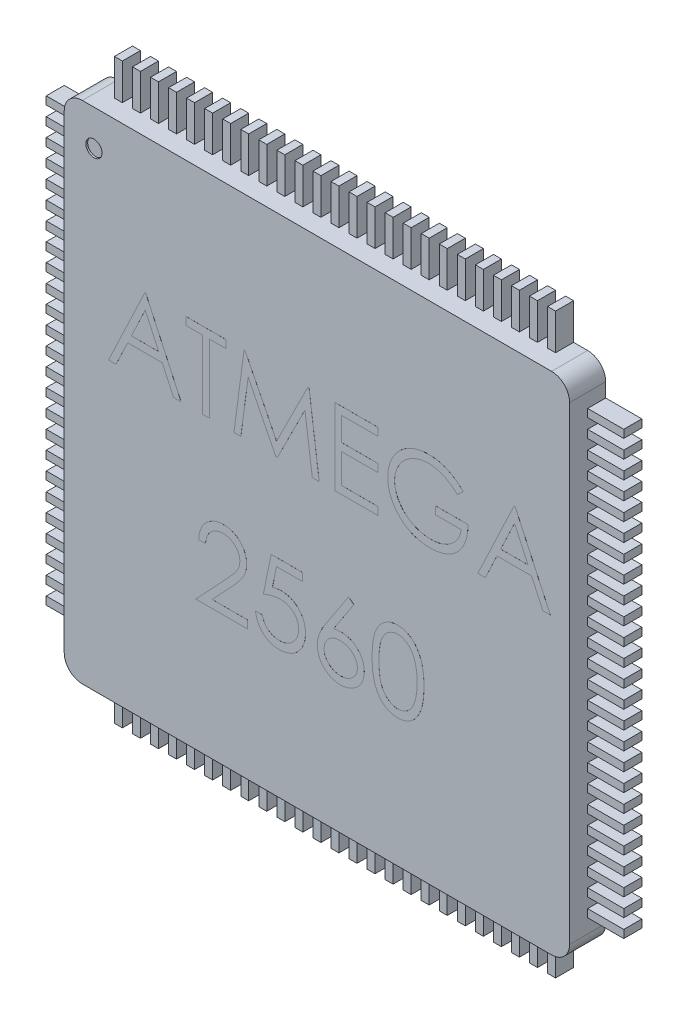
SolidWorks part; units mm, degrees
ref_plane "Plan de face" through (0, 0, 0) normal (0, 0, 1) x (1, 0, 0)
ref_plane "Plan de dessus" through (0, 0, 0) normal (0, 1, 0) x (1, 0, 0)
ref_plane "Plan de droite" through (0, 0, 0) normal (1, 0, 0) x (0, 0, -1)
sketch "Sketch1" plane through (0, 0, 0) normal (0, 0, 1) x (1, 0, 0)
  line L1 (6.5, 7) -> (-6.5, 7)
  line L2 (7, 6.5) -> (7, -6.5)
  line L3 (6.5, -7) -> (-6.5, -7)
  line L4 (-7, 6.5) -> (-7, -6.5)
  line L5 (7, 7) -> (-7, -7) construction
  line L6 (7, -7) -> (-7, 7) construction
  line L7 (-8, 8) -> (8, 8) construction
  line L8 (-8, 8) -> (-8, -8) construction
  line L9 (-8, -8) -> (8, -8) construction
  line L10 (8, 8) -> (8, -8) construction
  line L11 (-8, 8) -> (8, -8) construction
  line L12 (-8, -8) -> (8, 8) construction
  arc A0 (-6.5, -7) -> (-7, -6.5) centre (-6.5, -6.5) cw
  arc A1 (7, -6.5) -> (6.5, -7) centre (6.5, -6.5) cw
  arc A2 (6.5, 7) -> (7, 6.5) centre (6.5, 6.5) cw
  arc A3 (-6.5, 7) -> (-7, 6.5) centre (-6.5, 6.5) ccw
  point P0 (0, 0)
  point P6 (0, 0)
  dimension "D5" = 0.5
  dimension "D1" = 14
  dimension "D2" = 14
  dimension "D3" = 16
  dimension "D4" = 16
extrude "Boss-Extrude1" add sketch "Sketch1" along normal blind 1
sketch "Sketch3" plane through (0, 0, 0) normal (0, 0, 1) x (1, 0, 0)
  line L0 (7, 0) -> (-7, 0) construction
  line L1 (7, -6.5) -> (7, 6.5) construction
  line L2 (-7, 6.5) -> (-7, -6.5) construction
  line L3 (0, 7) -> (0, -7) construction
  line L6 (7, -0.11) -> (8, -0.11)
  line L7 (8, -0.11) -> (8, 0.11)
  line L8 (8, 0.11) -> (7, 0.11)
  line L9 (7, 0.11) -> (7, -0.11)
  line L10 (7, 0.39) -> (8, 0.39)
  line L11 (8, 0.39) -> (8, 0.61)
  line L12 (8, 0.61) -> (7, 0.61)
  line L13 (7, 0.61) -> (7, 0.39)
  line L14 (7, 0.89) -> (8, 0.89)
  line L15 (8, 0.89) -> (8, 1.11)
  line L16 (8, 1.11) -> (7, 1.11)
  line L17 (7, 1.11) -> (7, 0.89)
  line L18 (7, 1.39) -> (8, 1.39)
  line L19 (8, 1.39) -> (8, 1.61)
  line L20 (8, 1.61) -> (7, 1.61)
  line L21 (7, 1.61) -> (7, 1.39)
  line L22 (7, 1.89) -> (8, 1.89)
  line L23 (8, 1.89) -> (8, 2.11)
  line L24 (8, 2.11) -> (7, 2.11)
  line L25 (7, 2.11) -> (7, 1.89)
  line L26 (7, 2.39) -> (8, 2.39)
  line L27 (8, 2.39) -> (8, 2.61)
  line L28 (8, 2.61) -> (7, 2.61)
  line L29 (7, 2.61) -> (7, 2.39)
  line L30 (7, 2.89) -> (8, 2.89)
  line L31 (8, 2.89) -> (8, 3.11)
  line L32 (8, 3.11) -> (7, 3.11)
  line L33 (7, 3.11) -> (7, 2.89)
  line L34 (7, 3.39) -> (8, 3.39)
  line L35 (8, 3.39) -> (8, 3.61)
  line L36 (8, 3.61) -> (7, 3.61)
  line L37 (7, 3.61) -> (7, 3.39)
  line L38 (7, 3.89) -> (8, 3.89)
  line L39 (8, 3.89) -> (8, 4.11)
  line L40 (8, 4.11) -> (7, 4.11)
  line L41 (7, 4.11) -> (7, 3.89)
  line L42 (7, 4.39) -> (8, 4.39)
  line L43 (8, 4.39) -> (8, 4.61)
  line L44 (8, 4.61) -> (7, 4.61)
  line L45 (7, 4.61) -> (7, 4.39)
  line L46 (7, 4.89) -> (8, 4.89)
  line L47 (8, 4.89) -> (8, 5.11)
  line L48 (8, 5.11) -> (7, 5.11)
  line L49 (7, 5.11) -> (7, 4.89)
  line L50 (7, 5.39) -> (8, 5.39)
  line L51 (8, 5.39) -> (8, 5.61)
  line L52 (8, 5.61) -> (7, 5.61)
  line L53 (7, 5.61) -> (7, 5.39)
  line L54 (7, 5.89) -> (8, 5.89)
  line L55 (8, 5.89) -> (8, 6.11)
  line L56 (8, 6.11) -> (7, 6.11)
  line L57 (7, 6.11) -> (7, 5.89)
  line L58 (7, -6.11) -> (7, -5.89)
  line L59 (8, -6.11) -> (7, -6.11)
  line L60 (8, -5.89) -> (8, -6.11)
  line L61 (7, -5.89) -> (8, -5.89)
  line L62 (7, -5.61) -> (7, -5.39)
  line L63 (8, -5.61) -> (7, -5.61)
  line L64 (8, -5.39) -> (8, -5.61)
  line L65 (7, -5.39) -> (8, -5.39)
  line L66 (7, -5.11) -> (7, -4.89)
  line L67 (8, -5.11) -> (7, -5.11)
  line L68 (8, -4.89) -> (8, -5.11)
  line L69 (7, -4.89) -> (8, -4.89)
  line L70 (7, -4.61) -> (7, -4.39)
  line L71 (8, -4.61) -> (7, -4.61)
  line L72 (8, -4.39) -> (8, -4.61)
  line L73 (7, -4.39) -> (8, -4.39)
  line L74 (7, -4.11) -> (7, -3.89)
  line L75 (8, -4.11) -> (7, -4.11)
  line L76 (8, -3.89) -> (8, -4.11)
  line L77 (7, -3.89) -> (8, -3.89)
  line L78 (7, -3.61) -> (7, -3.39)
  line L79 (8, -3.61) -> (7, -3.61)
  line L80 (8, -3.39) -> (8, -3.61)
  line L81 (7, -3.39) -> (8, -3.39)
  line L82 (7, -3.11) -> (7, -2.89)
  line L83 (8, -3.11) -> (7, -3.11)
  line L84 (8, -2.89) -> (8, -3.11)
  line L85 (7, -2.89) -> (8, -2.89)
  line L86 (7, -2.61) -> (7, -2.39)
  line L87 (8, -2.61) -> (7, -2.61)
  line L88 (8, -2.39) -> (8, -2.61)
  line L89 (7, -2.39) -> (8, -2.39)
  line L90 (7, -2.11) -> (7, -1.89)
  line L91 (8, -2.11) -> (7, -2.11)
  line L92 (8, -1.89) -> (8, -2.11)
  line L93 (7, -1.89) -> (8, -1.89)
  line L94 (7, -1.61) -> (7, -1.39)
  line L95 (8, -1.61) -> (7, -1.61)
  line L96 (8, -1.39) -> (8, -1.61)
  line L97 (7, -1.39) -> (8, -1.39)
  line L98 (7, -1.11) -> (7, -0.89)
  line L99 (8, -1.11) -> (7, -1.11)
  line L100 (8, -0.89) -> (8, -1.11)
  line L101 (7, -0.89) -> (8, -0.89)
  line L102 (7, -0.61) -> (7, -0.39)
  line L103 (8, -0.61) -> (7, -0.61)
  line L104 (8, -0.39) -> (8, -0.61)
  line L105 (7, -0.39) -> (8, -0.39)
  line L106 (-7, -0.39) -> (-8, -0.39)
  line L107 (-8, -0.39) -> (-8, -0.61)
  line L108 (-8, -0.61) -> (-7, -0.61)
  line L109 (-7, -0.61) -> (-7, -0.39)
  line L110 (-7, -0.89) -> (-8, -0.89)
  line L111 (-8, -0.89) -> (-8, -1.11)
  line L112 (-8, -1.11) -> (-7, -1.11)
  line L113 (-7, -1.11) -> (-7, -0.89)
  line L114 (-7, -1.39) -> (-8, -1.39)
  line L115 (-8, -1.39) -> (-8, -1.61)
  line L116 (-8, -1.61) -> (-7, -1.61)
  line L117 (-7, -1.61) -> (-7, -1.39)
  line L118 (-7, -1.89) -> (-8, -1.89)
  line L119 (-8, -1.89) -> (-8, -2.11)
  line L120 (-8, -2.11) -> (-7, -2.11)
  line L121 (-7, -2.11) -> (-7, -1.89)
  line L122 (-7, -2.39) -> (-8, -2.39)
  line L123 (-8, -2.39) -> (-8, -2.61)
  line L124 (-8, -2.61) -> (-7, -2.61)
  line L125 (-7, -2.61) -> (-7, -2.39)
  line L126 (-7, -2.89) -> (-8, -2.89)
  line L127 (-8, -2.89) -> (-8, -3.11)
  line L128 (-8, -3.11) -> (-7, -3.11)
  line L129 (-7, -3.11) -> (-7, -2.89)
  line L130 (-7, -3.39) -> (-8, -3.39)
  line L131 (-8, -3.39) -> (-8, -3.61)
  line L132 (-8, -3.61) -> (-7, -3.61)
  line L133 (-7, -3.61) -> (-7, -3.39)
  line L134 (-7, -3.89) -> (-8, -3.89)
  line L135 (-8, -3.89) -> (-8, -4.11)
  line L136 (-8, -4.11) -> (-7, -4.11)
  line L137 (-7, -4.11) -> (-7, -3.89)
  line L138 (-7, -4.39) -> (-8, -4.39)
  line L139 (-8, -4.39) -> (-8, -4.61)
  line L140 (-8, -4.61) -> (-7, -4.61)
  line L141 (-7, -4.61) -> (-7, -4.39)
  line L142 (-7, -4.89) -> (-8, -4.89)
  line L143 (-8, -4.89) -> (-8, -5.11)
  line L144 (-8, -5.11) -> (-7, -5.11)
  line L145 (-7, -5.11) -> (-7, -4.89)
  line L146 (-7, -5.39) -> (-8, -5.39)
  line L147 (-8, -5.39) -> (-8, -5.61)
  line L148 (-8, -5.61) -> (-7, -5.61)
  line L149 (-7, -5.61) -> (-7, -5.39)
  line L150 (-7, -5.89) -> (-8, -5.89)
  line L151 (-8, -5.89) -> (-8, -6.11)
  line L152 (-8, -6.11) -> (-7, -6.11)
  line L153 (-7, -6.11) -> (-7, -5.89)
  line L154 (-7, 6.11) -> (-7, 5.89)
  line L155 (-8, 6.11) -> (-7, 6.11)
  line L156 (-8, 5.89) -> (-8, 6.11)
  line L157 (-7, 5.89) -> (-8, 5.89)
  line L158 (-7, 5.61) -> (-7, 5.39)
  line L159 (-8, 5.61) -> (-7, 5.61)
  line L160 (-8, 5.39) -> (-8, 5.61)
  line L161 (-7, 5.39) -> (-8, 5.39)
  line L162 (-7, 5.11) -> (-7, 4.89)
  line L163 (-8, 5.11) -> (-7, 5.11)
  line L164 (-8, 4.89) -> (-8, 5.11)
  line L165 (-7, 4.89) -> (-8, 4.89)
  line L166 (-7, 4.61) -> (-7, 4.39)
  line L167 (-8, 4.61) -> (-7, 4.61)
  line L168 (-8, 4.39) -> (-8, 4.61)
  line L169 (-7, 4.39) -> (-8, 4.39)
  line L170 (-7, 4.11) -> (-7, 3.89)
  line L171 (-8, 4.11) -> (-7, 4.11)
  line L172 (-8, 3.89) -> (-8, 4.11)
  line L173 (-7, 3.89) -> (-8, 3.89)
  line L174 (-7, 3.61) -> (-7, 3.39)
  line L175 (-8, 3.61) -> (-7, 3.61)
  line L176 (-8, 3.39) -> (-8, 3.61)
  line L177 (-7, 3.39) -> (-8, 3.39)
  line L178 (-7, 3.11) -> (-7, 2.89)
  line L179 (-8, 3.11) -> (-7, 3.11)
  line L180 (-8, 2.89) -> (-8, 3.11)
  line L181 (-7, 2.89) -> (-8, 2.89)
  line L182 (-7, 2.61) -> (-7, 2.39)
  line L183 (-8, 2.61) -> (-7, 2.61)
  line L184 (-8, 2.39) -> (-8, 2.61)
  line L185 (-7, 2.39) -> (-8, 2.39)
  line L186 (-7, 2.11) -> (-7, 1.89)
  line L187 (-8, 2.11) -> (-7, 2.11)
  line L188 (-8, 1.89) -> (-8, 2.11)
  line L189 (-7, 1.89) -> (-8, 1.89)
  line L190 (-7, 1.61) -> (-7, 1.39)
  line L191 (-8, 1.61) -> (-7, 1.61)
  line L192 (-8, 1.39) -> (-8, 1.61)
  line L193 (-7, 1.39) -> (-8, 1.39)
  line L194 (-7, 1.11) -> (-7, 0.89)
  line L195 (-8, 1.11) -> (-7, 1.11)
  line L196 (-8, 0.89) -> (-8, 1.11)
  line L197 (-7, 0.89) -> (-8, 0.89)
  line L198 (-7, 0.61) -> (-7, 0.39)
  line L199 (-8, 0.61) -> (-7, 0.61)
  line L200 (-8, 0.39) -> (-8, 0.61)
  line L201 (-7, 0.39) -> (-8, 0.39)
  line L202 (-7, 0.11) -> (-7, -0.11)
  line L203 (-8, 0.11) -> (-7, 0.11)
  line L204 (-8, -0.11) -> (-8, 0.11)
  line L205 (-7, -0.11) -> (-8, -0.11)
  line L206 (0.11, 7) -> (0.11, 8)
  line L207 (-7, 0) -> (7, 0) construction
  line L208 (0.11, 8) -> (-0.11, 8)
  line L209 (-0.11, 8) -> (-0.11, 7)
  line L210 (-0.11, 7) -> (0.11, 7)
  line L211 (-0.39, 7) -> (-0.39, 8)
  line L212 (-0.39, 8) -> (-0.61, 8)
  line L213 (-0.61, 8) -> (-0.61, 7)
  line L214 (-0.61, 7) -> (-0.39, 7)
  line L215 (-0.89, 7) -> (-0.89, 8)
  line L216 (-0.89, 8) -> (-1.11, 8)
  line L217 (-1.11, 8) -> (-1.11, 7)
  line L218 (-1.11, 7) -> (-0.89, 7)
  line L219 (-1.39, 7) -> (-1.39, 8)
  line L220 (-1.39, 8) -> (-1.61, 8)
  line L221 (-1.61, 8) -> (-1.61, 7)
  line L222 (-1.61, 7) -> (-1.39, 7)
  line L223 (-1.89, 7) -> (-1.89, 8)
  line L224 (-1.89, 8) -> (-2.11, 8)
  line L225 (-2.11, 8) -> (-2.11, 7)
  line L226 (-2.11, 7) -> (-1.89, 7)
  line L227 (-2.39, 7) -> (-2.39, 8)
  line L228 (-2.39, 8) -> (-2.61, 8)
  line L229 (-2.61, 8) -> (-2.61, 7)
  line L230 (-2.61, 7) -> (-2.39, 7)
  line L231 (-2.89, 7) -> (-2.89, 8)
  line L232 (-2.89, 8) -> (-3.11, 8)
  line L233 (-3.11, 8) -> (-3.11, 7)
  line L234 (-3.11, 7) -> (-2.89, 7)
  line L235 (-3.39, 7) -> (-3.39, 8)
  line L236 (-3.39, 8) -> (-3.61, 8)
  line L237 (-3.61, 8) -> (-3.61, 7)
  line L238 (-3.61, 7) -> (-3.39, 7)
  line L239 (-3.89, 7) -> (-3.89, 8)
  line L240 (-3.89, 8) -> (-4.11, 8)
  line L241 (-4.11, 8) -> (-4.11, 7)
  line L242 (-4.11, 7) -> (-3.89, 7)
  line L243 (-4.39, 7) -> (-4.39, 8)
  line L244 (-4.39, 8) -> (-4.61, 8)
  line L245 (-4.61, 8) -> (-4.61, 7)
  line L246 (-4.61, 7) -> (-4.39, 7)
  line L247 (-4.89, 7) -> (-4.89, 8)
  line L248 (-4.89, 8) -> (-5.11, 8)
  line L249 (-5.11, 8) -> (-5.11, 7)
  line L250 (-5.11, 7) -> (-4.89, 7)
  line L251 (-5.39, 7) -> (-5.39, 8)
  line L252 (-5.39, 8) -> (-5.61, 8)
  line L253 (-5.61, 8) -> (-5.61, 7)
  line L254 (-5.61, 7) -> (-5.39, 7)
  line L255 (-5.89, 7) -> (-5.89, 8)
  line L256 (-5.89, 8) -> (-6.11, 8)
  line L257 (-6.11, 8) -> (-6.11, 7)
  line L258 (-6.11, 7) -> (-5.89, 7)
  line L259 (6.11, 7) -> (5.89, 7)
  line L260 (6.11, 8) -> (6.11, 7)
  line L261 (5.89, 8) -> (6.11, 8)
  line L262 (5.89, 7) -> (5.89, 8)
  line L263 (5.61, 7) -> (5.39, 7)
  line L264 (5.61, 8) -> (5.61, 7)
  line L265 (5.39, 8) -> (5.61, 8)
  line L266 (5.39, 7) -> (5.39, 8)
  line L267 (5.11, 7) -> (4.89, 7)
  line L268 (5.11, 8) -> (5.11, 7)
  line L269 (4.89, 8) -> (5.11, 8)
  line L270 (4.89, 7) -> (4.89, 8)
  line L271 (4.61, 7) -> (4.39, 7)
  line L272 (4.61, 8) -> (4.61, 7)
  line L273 (4.39, 8) -> (4.61, 8)
  line L274 (4.39, 7) -> (4.39, 8)
  line L275 (4.11, 7) -> (3.89, 7)
  line L276 (4.11, 8) -> (4.11, 7)
  line L277 (3.89, 8) -> (4.11, 8)
  line L278 (3.89, 7) -> (3.89, 8)
  line L279 (3.61, 7) -> (3.39, 7)
  line L280 (3.61, 8) -> (3.61, 7)
  line L281 (3.39, 8) -> (3.61, 8)
  line L282 (3.39, 7) -> (3.39, 8)
  line L283 (3.11, 7) -> (2.89, 7)
  line L284 (3.11, 8) -> (3.11, 7)
  line L285 (2.89, 8) -> (3.11, 8)
  line L286 (2.89, 7) -> (2.89, 8)
  line L287 (2.61, 7) -> (2.39, 7)
  line L288 (2.61, 8) -> (2.61, 7)
  line L289 (2.39, 8) -> (2.61, 8)
  line L290 (2.39, 7) -> (2.39, 8)
  line L291 (2.11, 7) -> (1.89, 7)
  line L292 (2.11, 8) -> (2.11, 7)
  line L293 (1.89, 8) -> (2.11, 8)
  line L294 (1.89, 7) -> (1.89, 8)
  line L295 (1.61, 7) -> (1.39, 7)
  line L296 (1.61, 8) -> (1.61, 7)
  line L297 (1.39, 8) -> (1.61, 8)
  line L298 (1.39, 7) -> (1.39, 8)
  line L299 (1.11, 7) -> (0.89, 7)
  line L300 (1.11, 8) -> (1.11, 7)
  line L301 (0.89, 8) -> (1.11, 8)
  line L302 (0.89, 7) -> (0.89, 8)
  line L303 (0.61, 7) -> (0.39, 7)
  line L304 (0.61, 8) -> (0.61, 7)
  line L305 (0.39, 8) -> (0.61, 8)
  line L306 (0.39, 7) -> (0.39, 8)
  line L307 (0.39, -7) -> (0.39, -8)
  line L308 (0.39, -8) -> (0.61, -8)
  line L309 (0.61, -8) -> (0.61, -7)
  line L310 (0.61, -7) -> (0.39, -7)
  line L311 (0.89, -7) -> (0.89, -8)
  line L312 (0.89, -8) -> (1.11, -8)
  line L313 (1.11, -8) -> (1.11, -7)
  line L314 (1.11, -7) -> (0.89, -7)
  line L315 (1.39, -7) -> (1.39, -8)
  line L316 (1.39, -8) -> (1.61, -8)
  line L317 (1.61, -8) -> (1.61, -7)
  line L318 (1.61, -7) -> (1.39, -7)
  line L319 (1.89, -7) -> (1.89, -8)
  line L320 (1.89, -8) -> (2.11, -8)
  line L321 (2.11, -8) -> (2.11, -7)
  line L322 (2.11, -7) -> (1.89, -7)
  line L323 (2.39, -7) -> (2.39, -8)
  line L324 (2.39, -8) -> (2.61, -8)
  line L325 (2.61, -8) -> (2.61, -7)
  line L326 (2.61, -7) -> (2.39, -7)
  line L327 (2.89, -7) -> (2.89, -8)
  line L328 (2.89, -8) -> (3.11, -8)
  line L329 (3.11, -8) -> (3.11, -7)
  line L330 (3.11, -7) -> (2.89, -7)
  line L331 (3.39, -7) -> (3.39, -8)
  line L332 (3.39, -8) -> (3.61, -8)
  line L333 (3.61, -8) -> (3.61, -7)
  line L334 (3.61, -7) -> (3.39, -7)
  line L335 (3.89, -7) -> (3.89, -8)
  line L336 (3.89, -8) -> (4.11, -8)
  line L337 (4.11, -8) -> (4.11, -7)
  line L338 (4.11, -7) -> (3.89, -7)
  line L339 (4.39, -7) -> (4.39, -8)
  line L340 (4.39, -8) -> (4.61, -8)
  line L341 (4.61, -8) -> (4.61, -7)
  line L342 (4.61, -7) -> (4.39, -7)
  line L343 (4.89, -7) -> (4.89, -8)
  line L344 (4.89, -8) -> (5.11, -8)
  line L345 (5.11, -8) -> (5.11, -7)
  line L346 (5.11, -7) -> (4.89, -7)
  line L347 (5.39, -7) -> (5.39, -8)
  line L348 (5.39, -8) -> (5.61, -8)
  line L349 (5.61, -8) -> (5.61, -7)
  line L350 (5.61, -7) -> (5.39, -7)
  line L351 (5.89, -7) -> (5.89, -8)
  line L352 (5.89, -8) -> (6.11, -8)
  line L353 (6.11, -8) -> (6.11, -7)
  line L354 (6.11, -7) -> (5.89, -7)
  line L355 (-6.11, -7) -> (-5.89, -7)
  line L356 (-6.11, -8) -> (-6.11, -7)
  line L357 (-5.89, -8) -> (-6.11, -8)
  line L358 (-5.89, -7) -> (-5.89, -8)
  line L359 (-5.61, -7) -> (-5.39, -7)
  line L360 (-5.61, -8) -> (-5.61, -7)
  line L361 (-5.39, -8) -> (-5.61, -8)
  line L362 (-5.39, -7) -> (-5.39, -8)
  line L363 (-5.11, -7) -> (-4.89, -7)
  line L364 (-5.11, -8) -> (-5.11, -7)
  line L365 (-4.89, -8) -> (-5.11, -8)
  line L366 (-4.89, -7) -> (-4.89, -8)
  line L367 (-4.61, -7) -> (-4.39, -7)
  line L368 (-4.61, -8) -> (-4.61, -7)
  line L369 (-4.39, -8) -> (-4.61, -8)
  line L370 (-4.39, -7) -> (-4.39, -8)
  line L371 (-4.11, -7) -> (-3.89, -7)
  line L372 (-4.11, -8) -> (-4.11, -7)
  line L373 (-3.89, -8) -> (-4.11, -8)
  line L374 (-3.89, -7) -> (-3.89, -8)
  line L375 (-3.61, -7) -> (-3.39, -7)
  line L376 (-3.61, -8) -> (-3.61, -7)
  line L377 (-3.39, -8) -> (-3.61, -8)
  line L378 (-3.39, -7) -> (-3.39, -8)
  line L379 (-3.11, -7) -> (-2.89, -7)
  line L380 (-3.11, -8) -> (-3.11, -7)
  line L381 (-2.89, -8) -> (-3.11, -8)
  line L382 (-2.89, -7) -> (-2.89, -8)
  line L383 (-2.61, -7) -> (-2.39, -7)
  line L384 (-2.61, -8) -> (-2.61, -7)
  line L385 (-2.39, -8) -> (-2.61, -8)
  line L386 (-2.39, -7) -> (-2.39, -8)
  line L387 (-2.11, -7) -> (-1.89, -7)
  line L388 (-2.11, -8) -> (-2.11, -7)
  line L389 (-1.89, -8) -> (-2.11, -8)
  line L390 (-1.89, -7) -> (-1.89, -8)
  line L391 (-1.61, -7) -> (-1.39, -7)
  line L392 (-1.61, -8) -> (-1.61, -7)
  line L393 (-1.39, -8) -> (-1.61, -8)
  line L394 (-1.39, -7) -> (-1.39, -8)
  line L395 (-1.11, -7) -> (-0.89, -7)
  line L396 (-1.11, -8) -> (-1.11, -7)
  line L397 (-0.89, -8) -> (-1.11, -8)
  line L398 (-0.89, -7) -> (-0.89, -8)
  line L399 (-0.61, -7) -> (-0.39, -7)
  line L400 (-0.61, -8) -> (-0.61, -7)
  line L401 (-0.39, -8) -> (-0.61, -8)
  line L402 (-0.39, -7) -> (-0.39, -8)
  line L403 (-0.11, -7) -> (0.11, -7)
  line L404 (-0.11, -8) -> (-0.11, -7)
  line L405 (0.11, -8) -> (-0.11, -8)
  line L406 (0.11, -7) -> (0.11, -8)
  line L407 (0, -7) -> (0, 7) construction
  dimension "D1" = 0.22
  dimension "D3" = 0.22
  dimension "D4" = 1
  dimension "D5" = 1
  dimension "D2" = 13
extrude "Boss-Extrude2" add sketch "Sketch3" along normal blind 0.5
sketch "Sketch4" plane through (0, 0, 1) normal (0, 0, 1) x (1, 0, 0)
  text T0 "ATMEGA\r\n   2560" font "Century Gothic" height in points 8
extrude "Boss-Extrude3" add sketch "Sketch4" along normal blind 0.001
sketch "Sketch5" plane through (0, 0, 1) normal (0, 0, 1) x (1, 0, 0)
  circle A0 centre (-6.1778, 6.0103) radius 0.2239
extrude "Cut-Extrude2" cut sketch "Sketch5" against normal blind 0.05
